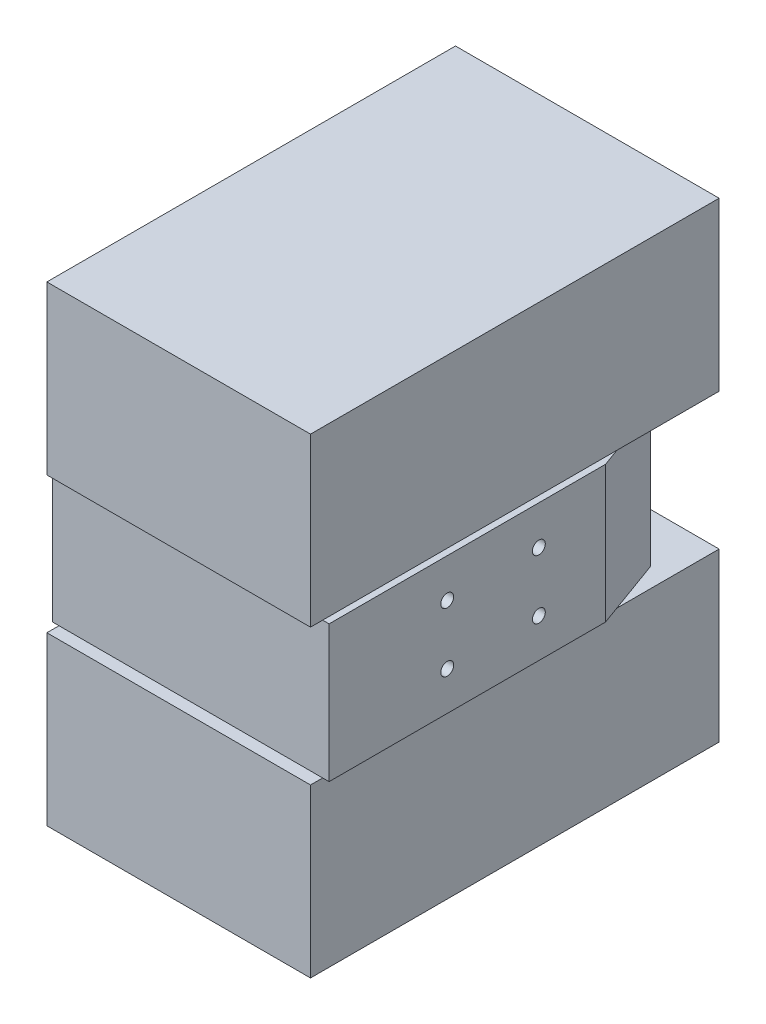
SolidWorks part; units mm, degrees
ref_plane "Front Plane" through (0, 0, 0) normal (0, 0, 1) x (1, 0, 0)
ref_plane "Top Plane" through (0, 0, 0) normal (0, 1, 0) x (1, 0, 0)
ref_plane "Right Plane" through (0, 0, 0) normal (1, 0, 0) x (0, 0, -1)
sketch "Sketch1" plane through (0, 0, 0) normal (0, 1, 0) x (1, 0, 0)
  line L0 (-43, -22) -> (-35, 0)
  line L1 (-43, -108) -> (43, -108)
  line L2 (-43, -108) -> (-43, -22)
  line L3 (-35, 0) -> (35, 0)
  line L4 (43, -108) -> (43, -22)
  line L5 (-43, -108) -> (37.0408, -5.6123) construction
  line L6 (-37.9751, -8.1816) -> (43, -108) construction
  line L7 (35, 0) -> (43, -22)
  line L8 (-61.5653, -102) -> (55.3549, -102) construction
  point P0 (-0.7958, -54.0127)
  point P1 (0, 0)
  dimension "D1" = 86
  dimension "D2" = 108
  dimension "D3" = 70
  dimension "D4" = 102
  dimension "D5" = 80
extrude "Boss-Extrude1" add sketch "Sketch1" along normal blind 21.25 and the other way blind 21.25
sketch "Sketch2" plane through (43, 0, 0) normal (1, 0, 0) x (0, 0, -1)
  line L0 (-108, 0) -> (0, 0) construction
  line L1 (-77, 18.2) -> (-37, 18.2) construction
  line L2 (-77, 18.2) -> (-77, -18.2) construction
  line L3 (-77, -18.2) -> (-37, -18.2) construction
  line L4 (-37, 18.2) -> (-37, -18.2) construction
  line L5 (-77, 18.2) -> (-37, -18.2) construction
  line L6 (-77, -18.2) -> (-37, 18.2) construction
  line L7 (-108, 21.25) -> (-108, -21.25) construction
  line L8 (0, 21.25) -> (0, -21.25) construction
  line L9 (-108, 21.25) -> (-22, 21.25) construction
  circle A0 centre (-71.25, 9.2) radius 2
  circle A1 centre (-42.75, 9.2) radius 2
  circle A2 centre (-42.75, -9.2) radius 2
  circle A3 centre (-71.25, -9.2) radius 2
  point P0 (-57, 0)
  point P17 (-41.7503, 33.2885)
  point P18 (0, 0)
  dimension "D5" = 4
  dimension "D8" = 4
  dimension "D1" = 40
  dimension "D2" = 36.4
  dimension "D3" = 31
  dimension "D4" = 5.75
  dimension "D6" = 12.05
  dimension "D7" = 5.75
extrude "Cut-Extrude1" cut sketch "Sketch2" against normal through all
sketch "Sketch3" plane through (0, 21.25, 0) normal (0, 1, 0) x (1, 0, 0)
  line L0 (35, 0) -> (-35, 0) construction
  line L1 (41, 15.32) -> (-41, 15.32)
  line L2 (41, 15.32) -> (41, -111.7742)
  line L3 (41, -111.7742) -> (-41, -111.7742)
  line L4 (-41, 15.32) -> (-41, -111.7742)
  line L5 (41, 15.32) -> (-41, -111.7742) construction
  line L6 (41, -111.7742) -> (-41, 15.32) construction
  point P0 (0, -48.2271)
  point P7 (2.7913, -20.0273)
  dimension "D1" = 15.32
  dimension "D2" = 82
extrude "Boss-Extrude2" add sketch "Sketch3" along normal blind 52
mirror "Mirror1" about plane through (0, 0, 0) normal (0, 1, 0) of "Boss-Extrude2"
